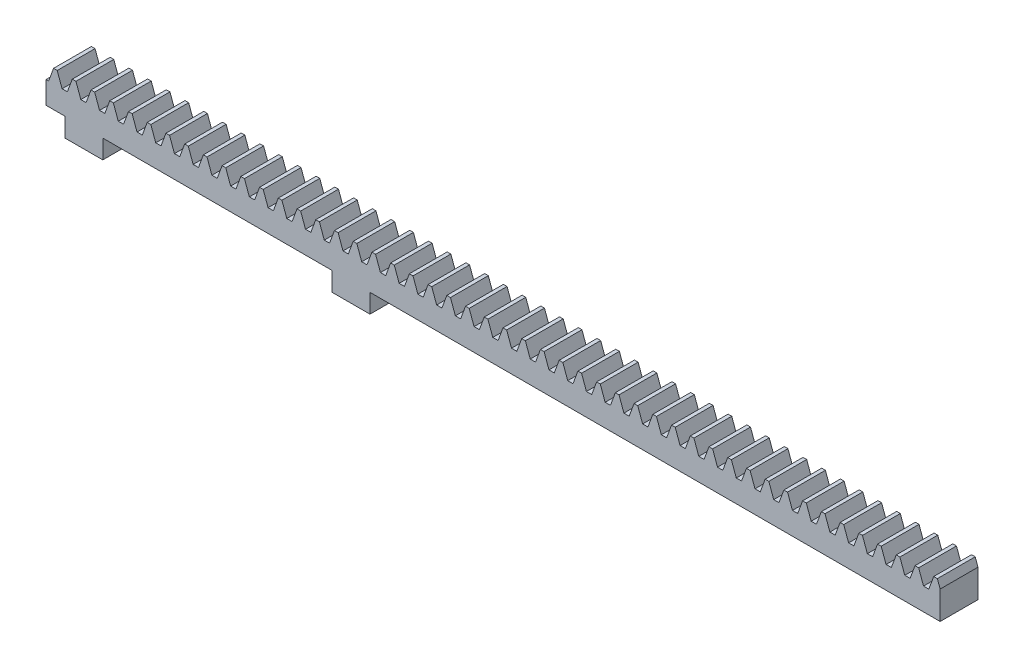
SolidWorks part; units mm, degrees
ref_plane "Plane1" through (0, 0, 0) normal (0, 0, 1) x (1, 0, 0)
ref_plane "Plane2" through (0, 0, 0) normal (0, 1, 0) x (1, 0, 0)
ref_plane "Plane3" through (0, 0, 0) normal (1, 0, 0) x (0, 0, -1)
sketch "HoldingSke" plane through (0, 0, 0) normal (0, 1, 0) x (1, 0, 0)
  line L0 (0, 0) -> (0.1392, 0.9903)
  line L1 (-15, 0) -> (100, 0) construction
  line L2 (0, 0) -> (-2.1039, 2.3779)
  line L3 (0, 0) -> (-11.863, 4.5341)
  line L4 (0, 0) -> (5.6657, 6.5177)
  line L5 (0, 0) -> (-23.7986, -8.8762)
  line L6 (0, 0) -> (-10.5278, -7.1032)
  line L9 (-71.009, 38.7566) -> (69.9449, 90.0596)
  line L10 (-76.2, 3.3779) -> (-71.2, 3.3779)
  line L11 (0, 0) -> (-6.35, 0)
  line L12 (-76.2, 101.6) -> (-76.162, 101.6)
  line L13 (24.9733, 27.94) -> (52.9518, 28.4284)
  line L14 (24.9733, 27.94) -> (24.9743, 27.94)
  line L15 (24.9733, 27.94) -> (100.4006, 29.5858)
  circle A0 centre (0, 0) radius 19.05
  circle A1 centre (0, 0) radius 2.5
  circle A2 centre (0, 0) radius 12.7
  dimension "MPH" = 5
  dimension "Diameter" = 38.1
  dimension "Num_teeth" = 49
  dimension "Pitch" = 1
  dimension "Width" = 6.35
  dimension "Show_teeth" = 998
  dimension "Thickness" = 12.7
  dimension "Ap" = 20
  dimension "Pitch_height" = 5
  dimension "Backlash" = 0.038
  dimension "Addendum_fac" = 1
  dimension "Dedendum_fac" = 1.25
  dimension "Clearance_fac" = 0.25
  dimension "Dedendum_add" = 0.001
  dimension "Length" = 150
  dimension "Module" = 1
sketch "BlankSke" plane through (0, 0, 0) normal (0, 0, 1) x (1, 0, 0)
  line L1 (0, 0) -> (150, 0)
  line L2 (0, 0) -> (0, 6)
  line L3 (0, 6) -> (150, 6)
  line L4 (150, 0) -> (150, 6)
  dimension "Length" = 150
  dimension "Blank_height" = 6
extrude "Blank" add sketch "BlankSke" against normal blind 6.35
sketch "TooCutSkeIll" plane through (0, 0, 0) normal (0, 0, 1) x (1, 0, 0)
  line L0 (-1.2538, 5.9737) -> (-0.5045, 3.9152)
  line L1 (-0.2687, 3.75) -> (0.2687, 3.75)
  line L2 (0.5045, 3.9152) -> (1.2538, 5.9737)
  line L3 (150, 6) -> (0, 6) construction
  line L4 (0, 0) -> (0, 64.897) construction
  line L5 (-13.208, 5) -> (12.954, 5) construction
  line L6 (0, 0) -> (150, 0) construction
  line L7 (0.8994, 5) -> (0.8994, 48.7463) construction
  line L8 (-0.8994, 5) -> (-0.8994, 48.7463) construction
  line L9 (1.2914, 6) -> (1.2914, 6.0254)
  line L10 (-1.2914, 6) -> (-1.2914, 6.0254)
  line L11 (-1.2914, 6.0254) -> (1.2914, 6.0254)
  arc A0 (0.2687, 3.75) -> (0.5045, 3.9152) centre (0.2687, 4.001) ccw
  arc A1 (-0.5045, 3.9152) -> (-0.2687, 3.75) centre (-0.2687, 4.001) ccw
  arc A2 (1.2914, 6) -> (1.2538, 5.9737) centre (1.2914, 5.96) ccw
  arc A3 (-1.2538, 5.9737) -> (-1.2914, 6) centre (-1.2914, 5.96) ccw
  dimension "Root_fillet" = 0.251
  dimension "Break_rad" = 0.04
  dimension "Pitch_height" = 5
  dimension "Gap_width" = 1.7988
  dimension "Dedendum" = 1.25
  dimension "Addendum_plus" = 1.0254
  dimension "Pressure_angle" = 20
extrude "ToothCutIll" [suppressed] cut sketch "TooCutSkeIll" against normal through all
sketch "TooCutSkeSim" plane through (0, 0, 0) normal (0, 0, 1) x (1, 0, 0)
  line L0 (0.4444, 3.75) -> (-0.4444, 3.75)
  line L1 (1.2726, 6.0254) -> (0.4444, 3.75)
  line L2 (0, 17.4625) -> (0, 53.467) construction
  line L3 (1.2726, 6.0254) -> (-1.2726, 6.0254)
  line L6 (-1.2726, 6.0254) -> (-0.4444, 3.75)
  line L9 (-0.8994, 5) -> (0.8994, 5) construction
  line L10 (0, 0) -> (150, 0) construction
  line L11 (0.8994, 5) -> (0.8994, 53.467) construction
  line L12 (-0.8994, 5) -> (-0.8994, 53.467) construction
  dimension "Pitch_height" = 5
  dimension "Pressure_angle" = 20
  dimension "Gap_width" = 1.7988
  dimension "Dedendum" = 1.25
  dimension "Addendum_plus" = 1.0254
extrude "ToothCutSim" cut sketch "TooCutSkeSim" against normal through all
pattern_linear "TeethCuts" count 49 spacing 3.1416 along (1, 0, 0) of "ToothCutIll", "ToothCutSim"
sketch "Sketch1" plane through (0, 0, 0) normal (0, -1, 0) x (1, 0, 0)
  line L0 (48, 0) -> (48, -6.35)
  line L1 (48, 0) -> (54.35, 0)
  line L2 (48, -6.35) -> (54.35, -6.35)
  line L3 (54.35, 0) -> (54.35, -6.35)
  line L6 (0, -6.35) -> (0, 0) construction
  line L7 (0, 0) -> (150, 0) construction
  line L8 (0, -6.35) -> (150, -6.35) construction
  line L9 (3.175, 0) -> (3.175, -6.35)
  line L10 (3.175, 0) -> (9.525, 0)
  line L11 (3.175, -6.35) -> (9.525, -6.35)
  line L12 (9.525, 0) -> (9.525, -6.35)
  dimension "D1" = 48
  dimension "D2" = 6.35
  dimension "D3" = 3.175
  dimension "D4" = 6.35
extrude "ElasticPegs_Extrude" add sketch "Sketch1" along normal blind 3.175
equation "' \"Module@HoldingSke\" = 6.35"
equation "' \"Num_teeth@HoldingSke\" = 12"
equation "' \"Ap@HoldingSke\" =  20"
equation "' \"Width@HoldingSke\" = 0.25 * 25.4"
equation "' \"Show_teeth@HoldingSke\" = 500"
equation "' \"Backlash@HoldingSke\" = 0.009 * 25.4"
equation "' \"Addendum_fac@HoldingSke\" = 1.0"
equation "' \"Dedendum_fac@HoldingSke\" = 1.25"
equation "' \"Dedendum_add@HoldingSke\" = 0.00005 * 25.4"
equation "' \"Clearance_fac@HoldingSke\" = 0.25"
equation "' \"Pitch_height@HoldingSke\" = 1 * 25.4"
equation "' \"Length@HoldingSke\" = 4.71 * 25.4"
equation "\"Pitch@HoldingSke\" = 1 / \"Module@HoldingSke\""
equation "\"MPH@HoldingSke\" = \"Dedendum_fac@HoldingSke\" / \"Pitch@HoldingSke\" + 2 * \"Dedendum_add@HoldingSke\" + 0.002 * 25.4"
equation "\"MPH@HoldingSke\" = ((sgn( \"MPH@HoldingSke\" - \"Pitch_height@HoldingSke\")+1)*( \"MPH@HoldingSke\" - \"Pitch_height@HoldingSke\"))/2 + \"Pitch_height@HoldingSke\""
equation "\"Blank_height@BlankSke\" = \"Pitch_height@HoldingSke\" + \"Addendum_fac@HoldingSke\"  / \"Pitch@HoldingSke\" "
equation "\"Length@BlankSke\" =  \"Length@HoldingSke\""
equation "\"Face_width@Blank\" = \"Width@HoldingSke\""
equation "\"Pressure_angle@TooCutSkeIll\" = \"Ap@HoldingSke\""
equation "\"Addendum_plus@TooCutSkeIll\" =  \"Addendum_fac@HoldingSke\"  / \"Pitch@HoldingSke\" + 0.001 *25.4"
equation "\"Dedendum@TooCutSkeIll\" = \"Dedendum_fac@HoldingSke\"  / \"Pitch@HoldingSke\""
equation "\"Pitch_height@TooCutSkeIll\" =  \"MPH@HoldingSke\""
equation "\"Gap_width@TooCutSkeIll\" = 3.14159265 / 2 / \"Pitch@HoldingSke\" + 6 * \"Backlash@HoldingSke\""
equation "\"Pressure_angle@TooCutSkeSim\" = \"Ap@HoldingSke\""
equation "\"Addendum_plus@TooCutSkeSim\" =  \"Addendum_fac@HoldingSke\"  / \"Pitch@HoldingSke\" + 0.001 * 25.4"
equation "\"Dedendum@TooCutSkeSim\" = \"Dedendum_fac@HoldingSke\"  / \"Pitch@HoldingSke\""
equation "\"Pitch_height@TooCutSkeSim\" =  \"MPH@HoldingSke\""
equation "\"Gap_width@TooCutSkeSim\" = 3.14159265 / 2 / \"Pitch@HoldingSke\" + 6 * \"Backlash@HoldingSke\""
equation "\"Root_fillet@TooCutSkeIll\" = \"Clearance_fac@HoldingSke\" / \"Pitch@HoldingSke\" + \"Dedendum_add@HoldingSke\""
equation "\"Break_rad@TooCutSkeIll\" = 0.02 / \"Pitch@HoldingSke\" * 2"
equation "\"Linear_pitch@TeethCuts\" = 3.14159265 / \"Pitch@HoldingSke\""
equation "\"Num_teeth@HoldingSke\" = int( ( \"Length@HoldingSke\" + 0 ) / (3.14159265 / \"Pitch@HoldingSke\")) + 0.9999  + 1"
equation " \"Num_teeth@TeethCuts\" = int( \"Show_teeth@HoldingSke\" ) + 1"
equation " \"Num_teeth@TeethCuts\" = ((sgn( \"Num_teeth@TeethCuts\" - \"Num_teeth@HoldingSke\" )-1)*( \"Num_teeth@TeethCuts\" - \"Num_teeth@HoldingSke\" ))/-2+ \"Num_teeth@HoldingSke\""
equation " \"Num_teeth@TeethCuts\" = ((sgn( \"Num_teeth@TeethCuts\" - 2.0)+1)*( \"Num_teeth@TeethCuts\" - 2.0))/2 +2.0"
equation "\"CageLeftBottomEdge\"=22.11mm"
equation "\"CageLeftTopEdge\"=22.11mm"
equation "\"CageRightBottomEdge\"=21.63mm"
equation "\"CageRightTopEdge\"=21.63mm"
equation "\"CageHeight\"=86.04mm"
equation "\"CageLength\"=73.76mm"
equation "\"CageTopScrewClearance\"=10mm"
equation "\"CageBottomScrewClearance\"=25mm"
equation "\"CageLeftTopDepth\"= 11.65mm"
equation "\"CageLeftBottomDepth\"=11.11mm"
equation "\"CageLeftTopHeight\"=8.56175mm"
equation "\"CageLeftBottomHeight\"=16mm"
equation "\"CageRightTopDepth\"= 11.05mm"
equation "\"CageRightBottomDepth\"=10.58mm"
equation "\"CageRightTopHeight\"=9.6mm"
equation "\"CageRightBottomHeight\"=15.49mm"
equation "\"CageLeftTopChannelDepth\"=2.41908mm"
equation "\"CageLeftBottomChannelDepth\"=2.588mm"
equation "\"CageLeftChannelHeight\"=11.7mm"
equation "\"CageRightTopChannelDepth\"=2.32mm"
equation "\"CageRightBottomChannelDepth\"=2.318mm"
equation "\"CageRightChannelHeight\"=10mm"
equation "\"CageChanRelHeight\"=23.99mm"
equation "\"CageChanRelDepth\"=5.492mm"
equation "\"CageChamberRadius\"=16.261mm"
equation "\"CageScrewDiameter\"=4.8mm"
equation "\"CageSetScrewDiameter\"=3.5mm"
equation "\"CageAxleRadius\"=6.639mm"
equation "\"CageAxleKeyHeight\"=1.619mm"
equation "\"CageAxleKeyWidth\"=2.662mm"
equation "\"CageHoseWindowWidth\"=16.29mm"
equation "\"CageHoseWindowHeight\"=26.5mm"
equation "\"CageHoseWindow-Edge\"=8.89mm"
equation "\"CageScrew-VerticalEdge\"=5.0mm"
equation "\"CageScrew-HorizontalEdge\"=7.5mm"
equation "\"CageScrew-HoseCornerScrewEdge\"=4.45mm"
equation "\"CageAxle-BottomEdge\"=56.05mm"
equation "\"CageAxle-FrontEdge\"=46.03mm"
equation "\"CageBackSetScrew-Axle\"=40mm"
equation "\"CageFrontSetScrew-Axle\"=22mm"
equation "\"CageVelocityWindow-BackEdge\"=34.8mm"
equation "\"CageVelocityWindow-BottomEdge\"=27.55mm"
equation "\"CageVelocityWindowHeight\"=22.29mm"
equation "\"CageVelocityWindowWidth\"=12.61mm"
equation "\"TriggerSlot-BottomEdge\"=6.35mm"
equation "\"TriggerSlot-FrontEdge\"=15mm"
equation "\"TriggerSlotSize\"=6.7mm"
equation "\"TriggerRackOffset\"=.236224in"
equation "\"TriggerSlotSizeInt\"=.25in"
equation "\"MotorMountLegLength\"=.25in"
equation "\"GearOffset\"=.264907in"
equation "\"TriggerSlotSpacing\"=.25in"
equation "\"TriggerMiniSlotWidth\"=3.5mm"
equation "\"TriggerRackWidth\"=6.5mm"
equation "\"TGMGearFaceDiameter\"=24.40mm"
equation "\"TGMCylinderLength\"=15.00mm"
equation "\"TGMScrewHole-Center\"=8.70mm"
equation "\"TGMScrewHoleDiameter\"=5.04mm"
equation "\"TGMCenterHoleDiameter\"=9.50mm"
equation "\"TGMShaftCollarSideLength\"=19.00mm"
equation "\"TGMShaftCollarDockingDepth\"=7.00mm"
equation "\"whitemotordepth\"=11.27mm"
equation "\"whitemotorbackdepth\"=3.845mm"
equation "\"whitemotoraxledepth\" = 3.5mm"
equation "\"whitemotoraxleoffset\"=11.4mm"
equation "\"whitemotorwidth\"=12.07mm"
equation "\"whitemotorheight\"=16.68mm"
equation "\"whitemotorcylinderlength\" =13.04mm"
equation "\"whitemotorcylinderradius\"=3.845mm"
equation "\"whitemotorcylinderoffset\"=2.35mm"
equation "\"whitemotorcutoutlength\"=1.88mm"
equation "\"whitemotorouterrad\"=5mm"
equation "\"whitemotorinnerrad\"=2.95mm"
equation "\"elasticracklength\"=2in"
equation "\"elasticrackpegsize\"=.25in"
equation "\"elasticrackpegbuffer\"=.125in"
equation "\"elasticrackpegspacing\"=1.76476378in"
equation "\"elasticbaybuffer\"=.25in"
equation "\"elasticdepth\"=.125in"
equation "\"elasticbaydepth\"=.75in"
equation "\"motormountwidth\"=12mm"
equation "\"motormountcornerfillet\"=3mm"
equation "\"D2@Sketch1\"=\"elasticrackpegsize\""
equation "\"D4@Sketch1\"=\"elasticrackpegsize\""
equation "\"D3@Sketch1\"=\"elasticrackpegsize\"/2"
equation "\"D1@Sketch1\"=\"elasticrackpegspacing\"+\"elasticrackpegsize\"/2"
equation "\"pandiscradius\"=14in"
equation "\"towermaterialwidth\"=.25in"
equation "\"towerslotlength\"=.5in"
equation "\"towermarkerspace\"=5in"
equation "\"towerslothorizoffset\"=1in"
equation "\"towerslothorizspacing\"=2in"
equation "\"towerslotvertoffset\"=3in"
equation "\"towerslotvertspacing\"=2in"
equation "\"towerheight\"=12in"
equation "\"towerupslot\"=1in"
equation "\"toweraxle\"=.5in"
equation "\"towerplatslotoffset\"=1.5in"
equation "\"towermotorpanelheight\"=10in"
equation "\"towerplatdepth\"=2in"
equation "\"stepperouterrad\"=10mm"
equation "\"stepperscrewsize\"=3.45mm"
equation "\"stepperscrewc2c\"=49.5mm"
equation "\"stepperdepthoffset\"=24mm"
equation "\"stepperhorizoffset\"=22.91mm"
